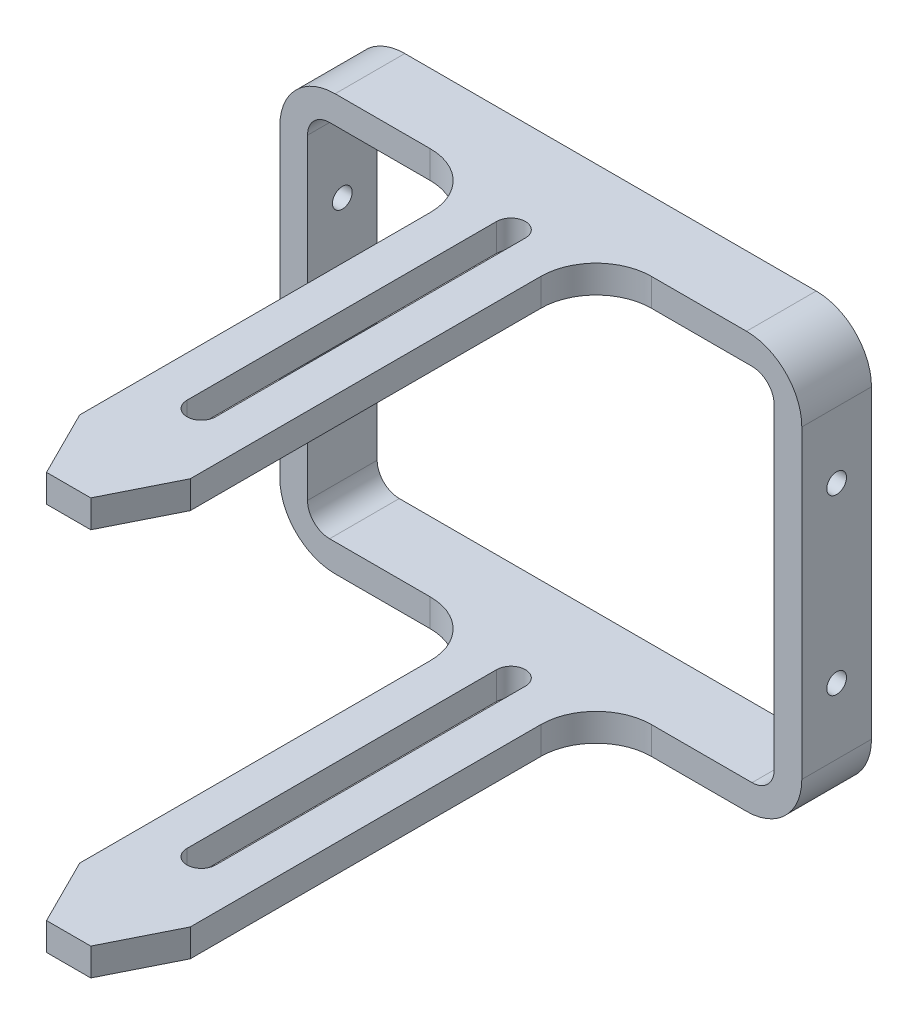
SolidWorks part; units mm, degrees
ref_plane "Front Plane" through (0, 0, 0) normal (0, 0, 1) x (1, 0, 0)
ref_plane "Top Plane" through (0, 0, 0) normal (0, 1, 0) x (1, 0, 0)
ref_plane "Right Plane" through (0, 0, 0) normal (1, 0, 0) x (0, 0, -1)
sketch "Sketch1" plane through (0, 0, 0) normal (0, 0, 1) x (1, 0, 0)
  line L1 (-29.972, -23.876) -> (29.972, -23.876)
  line L2 (-29.972, -23.876) -> (-29.972, 23.876)
  line L3 (-29.972, 23.876) -> (29.972, 23.876)
  line L4 (29.972, -23.876) -> (29.972, 23.876)
  line L5 (-29.972, -23.876) -> (29.972, 23.876) construction
  line L6 (-29.972, 23.876) -> (29.972, -23.876) construction
  line L7 (-26.797, -20.701) -> (26.797, -20.701)
  line L8 (-26.797, -20.701) -> (-26.797, 20.701)
  line L9 (-26.797, 20.701) -> (26.797, 20.701)
  line L10 (26.797, -20.701) -> (26.797, 20.701)
  line L11 (-26.797, -20.701) -> (26.797, 20.701) construction
  line L12 (-26.797, 20.701) -> (26.797, -20.701) construction
  point P0 (0, 0)
  point P6 (0, 0)
  dimension "D1" = 59.944
  dimension "D2" = 47.752
  dimension "D3" = 3.175
  dimension "D4" = 3.175
extrude "Boss-Extrude1" add sketch "Sketch1" along normal blind 8.001
sketch "Sketch2" plane through (0, 23.876, 0) normal (0, 1, 0) x (1, 0, 0)
  line L0 (-6.35, -8.001) -> (-6.35, -54.61)
  line L1 (-6.35, -54.61) -> (-2.54, -62.23)
  line L2 (-2.54, -62.23) -> (2.54, -62.23)
  line L3 (2.54, -62.23) -> (6.35, -54.61)
  line L4 (6.35, -54.61) -> (6.35, -8.001)
  line L5 (0, -4.4005) -> (0, 4.4005) construction
  line L6 (6.35, -8.001) -> (-6.35, -8.001)
  line L7 (29.972, -8.001) -> (-29.972, -8.001) construction
  point P2 (0, -8.001)
  point P8 (0, -62.23)
  dimension "D1" = 54.229
  dimension "D2" = 5.08
  dimension "D3" = 12.7
  dimension "D4" = 6.35
  dimension "D5" = 7.62
extrude "Boss-Extrude2" add sketch "Sketch2" against normal blind 3.175 contours L1 L2 L3 L4 L6 L0
sketch "Sketch3" plane through (0, 23.876, 0) normal (0, 1, 0) x (1, 0, 0)
  line L0 (0, -46.99) -> (0, -11.43) construction
  line L1 (-1.651, -46.99) -> (-1.651, -11.43)
  line L2 (1.651, -46.99) -> (1.651, -11.43)
  line L3 (0, -26.2636) -> (0, 26.2636) construction
  line L4 (-2.54, -62.23) -> (2.54, -62.23) construction
  arc A0 (-1.651, -46.99) -> (1.651, -46.99) centre (0, -46.99) ccw
  arc A1 (1.651, -11.43) -> (-1.651, -11.43) centre (0, -11.43) ccw
  point P2 (0, -29.21)
  dimension "D1" = 3.302
  dimension "D2" = 35.56
  dimension "D3" = 15.24
extrude "Cut-Extrude1" cut sketch "Sketch3" against normal blind 3.302
mirror "Mirror1" about plane through (0, 0, 0) normal (0, 1, 0) of "Cut-Extrude1", "Boss-Extrude2"
sketch "Sketch4" plane through (-29.972, 0, 0) normal (-1, 0, 0) x (0, 0, 1)
  line L0 (8.001, 23.876) -> (0, 23.876) construction
  line L1 (4.0005, 9.9441) -> (4.0005, -9.9441) construction
  line L2 (32.9692, 0) -> (-32.9692, 0) construction
  point P0 (4.0005, 9.9441)
  point P1 (4.0005, -9.9441)
  point P5 (4.0005, 23.876)
  point P7 (4.0005, 0)
  dimension "D1" = 19.8882
hole_wizard "#4-40 Tapped Hole1" positions "Sketch5" profile "Sketch7" tap size "#4-40" standard "ANSI Inch" end condition through all
sketch "Sketch5" plane through (-29.972, 0, 0) normal (-1, 0, 0) x (0, 0, 1)
  point P0 (4.0005, 9.9441)
  point P3 (4.0005, -9.9441)
sketch "Sketch7" plane through (-29.972, 9.9441, 4.0005) normal (0, 1, 0) x (0, 0, 1)
  line L0 (0, 0) -> (0, 59.944)
  line L1 (0, 59.944) -> (1.1303, 59.944)
  line L2 (1.1303, 59.944) -> (1.1303, 0)
  line L5 (1.1303, 0) -> (0, 0)
  line L11 (0, -6.35) -> (0, 107.95) construction
  dimension "Thru Tap Drill Dia." = 2.2606
  dimension "Thru Tap Drill Depth" = 59.944
cosmetic thread "Hole Thread1" parameters "D2"=2.8448
cosmetic thread "Hole Thread2" parameters "D2"=2.8448
fillet "Fillet1" radius 6.35 4 edges at (29.972, -23.876, 4.0005) (29.972, 23.876, 4.0005) (-29.972, -23.876, 4.0005) (-29.972, 23.876, 4.0005)
fillet "Fillet2" radius 2.54 4 edges at (-26.797, -20.701, 4.0005) (-26.797, 20.701, 4.0005) (26.797, -20.701, 4.0005) (26.797, 20.701, 4.0005)
fillet "Fillet3" radius 6.35 4 edges at (6.35, 22.2885, 8.001) (6.35, -22.2885, 8.001) (-6.35, 22.2885, 8.001) (-6.35, -22.2885, 8.001)
ref_plane "Plane1" through (0, 0, 0) normal (-1, 0, 0) x (0, 0, 1)
equation "\"square thickness\"= 0.125in"
equation "\"D3@Sketch1\"=\"square thickness\""
equation "\"D4@Sketch1\"=\"square thickness\""
equation "\"D1@Boss-Extrude2\"=\"square thickness\""
